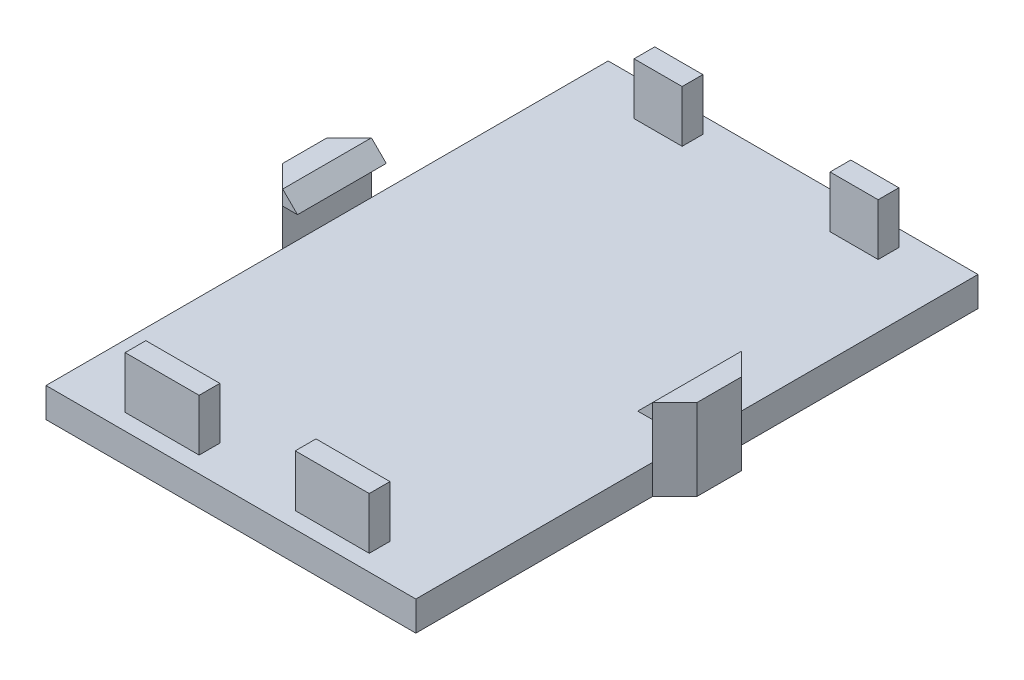
SolidWorks part; units mm, degrees
ref_plane "Front Plane" through (0, 0, 0) normal (0, 0, 1) x (1, 0, 0)
ref_plane "Top Plane" through (0, 0, 0) normal (0, 1, 0) x (1, 0, 0)
ref_plane "Right Plane" through (0, 0, 0) normal (1, 0, 0) x (0, 0, -1)
sketch "Sketch1" plane through (0, 0, 0) normal (0, 1, 0) x (1, 0, 0)
  line L0 (0, 0) -> (50000, 0) construction
  line L1 (-12.5, -19) -> (12.5, -19)
  line L2 (-12.5, -19) -> (-12.5, 19)
  line L3 (-12.5, 19) -> (12.5, 19)
  line L4 (12.5, -19) -> (12.5, 19)
  line L5 (-12.5, -19) -> (12.5, 19) construction
  line L6 (-12.5, 19) -> (12.5, -19) construction
  line L7 (0, 0) -> (0, 50000) construction
  line L8 (12.5, 3) -> (14, 1.5)
  line L9 (14, 1.5) -> (14, -1.5)
  line L10 (12.5, -3) -> (14, -1.5)
  line L11 (-12.5, -3) -> (-14, -1.5)
  line L12 (-14, 1.5) -> (-14, -1.5)
  line L13 (-12.5, 3) -> (-14, 1.5)
  line L14 (8.25, -16.5) -> (8.25, -17.9)
  line L15 (-8.25, 16.5) -> (8.25, 16.5)
  line L16 (-8.25, 16.5) -> (-8.25, 17.9)
  line L17 (-8.25, 17.9) -> (8.25, 17.9)
  line L18 (8.25, 16.5) -> (8.25, 17.9)
  line L19 (-8.25, 16.5) -> (8.25, 17.9) construction
  line L20 (-8.25, 17.9) -> (8.25, 16.5) construction
  line L21 (-8.25, -17.9) -> (8.25, -17.9)
  line L22 (-8.25, -16.5) -> (-8.25, -17.9)
  line L23 (-8.25, -16.5) -> (8.25, -16.5)
  point P0 (0, 0)
  point P15 (14, 0)
  point P20 (0, 17.2)
  dimension "D1" = 25
  dimension "D2" = 38
  dimension "D3" = 16
  dimension "D4" = 45
  dimension "D5" = 1.5
  dimension "D6" = 1.4
  dimension "D7" = 4.25
  dimension "D8" = 1.1
extrude "Boss-Extrude1" add sketch "Sketch1" along normal blind 2 contours L1 L4 L3 L2 region at (0, 0, 0)
extrude "Boss-Extrude2" add sketch "Sketch1<3>" along normal blind 5.5 contours L2 L13 L12 L11 | L4 L10 L9 L8 | L15 L18 L17 L16 | L23 L22 L21 L14 region at (-13.1667, 0, 0) region at (13.1667, 0, 0) region at (0, 0, 17.2) region at (0, 0, -17.2)
sketch "Sketch1<3>" plane through (0, 0, 0) normal (0, 1, 0) x (1, 0, 0) same geometry as "Sketch1"
sketch "Sketch2" plane through (0, 0, 0) normal (0, 0, 1) x (1, 0, 0)
  line L0 (12.5, 5.5) -> (11.5, 4.5)
  line L1 (11.5, 4.5) -> (12.5, 4.5)
  line L2 (12.5, 5.5) -> (12.5, 2) construction
  line L3 (12.5, 4.5) -> (12.5, 5.5)
  line L4 (0, -3.025) -> (0, 3.025) construction
  line L5 (-11.5, 4.5) -> (-12.5, 4.5)
  line L6 (-12.5, 4.5) -> (-12.5, 5.5)
  line L7 (-12.5, 5.5) -> (-11.5, 4.5)
  dimension "D1" = 1
extrude "Boss-Extrude3" add sketch "Sketch2" along normal up to vertex (3 mm away) and the other way up to vertex (3 mm away) up to point (12.5, 5.5, 3) other way up to point (12.5, 5.5, -3)
sketch "Sketch3" plane through (0, 2, 0) normal (0, 1, 0) x (1, 0, 0)
  line L0 (-8.25, -16.5) -> (8.25, -16.5) construction
  line L1 (-3.25, -17.9) -> (3.25, -17.9)
  line L2 (-3.25, -17.9) -> (-3.25, -16.5)
  line L3 (-3.25, -16.5) -> (3.25, -16.5)
  line L4 (3.25, -17.9) -> (3.25, -16.5)
  line L5 (-3.25, -17.9) -> (3.25, -16.5) construction
  line L6 (-3.25, -16.5) -> (3.25, -17.9) construction
  line L7 (-8.25, 17.9) -> (8.25, 17.9) construction
  line L8 (-5, 16.5) -> (5, 16.5)
  line L9 (-5, 16.5) -> (-5, 17.9)
  line L10 (-5, 17.9) -> (5, 17.9)
  line L11 (-12.5, -19) -> (12.5, -19) construction
  line L12 (5, 16.5) -> (5, 17.9)
  line L13 (-8.25, -17.9) -> (8.25, -17.9) construction
  line L14 (-5, 16.5) -> (5, 17.9) construction
  line L15 (-5, 17.9) -> (5, 16.5) construction
  line L16 (-8.25, 16.5) -> (8.25, 16.5) construction
  line L17 (-12.5, 19) -> (12.5, 19) construction
  point P0 (0, -17.2)
  point P7 (0, 17.2)
  point P21 (0, -19)
  point P23 (0, 19)
  dimension "D1" = 6.5
  dimension "D2" = 10
extrude "Cut-Extrude1" cut sketch "Sketch3" along normal up to surface (3.5 mm away) up to face at (0, 5.5, 17.2)
